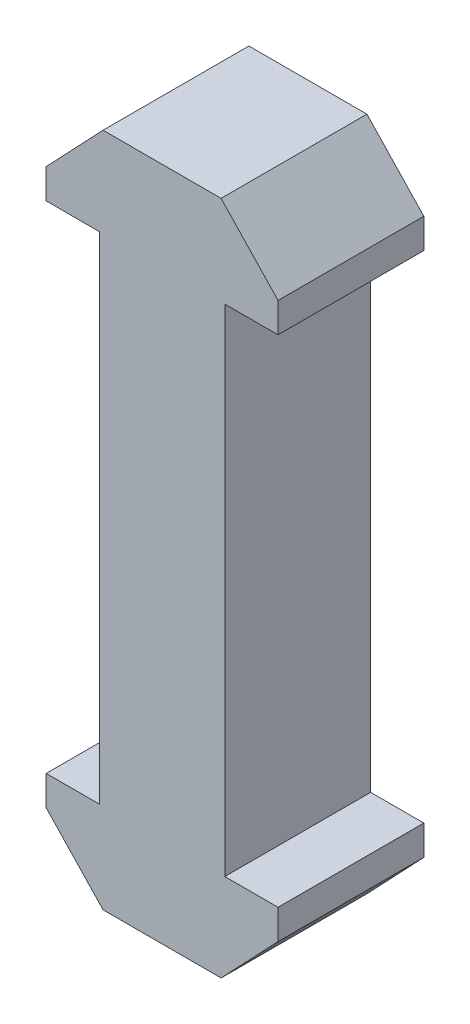
SolidWorks part; units mm, degrees
ref_plane "Front Plane" through (0, 0, 0) normal (0, 0, 1) x (1, 0, 0)
ref_plane "Top Plane" through (0, 0, 0) normal (0, 1, 0) x (1, 0, 0)
ref_plane "Right Plane" through (0, 0, 0) normal (1, 0, 0) x (0, 0, -1)
sketch "Sketch1" plane through (0, 0, 0) normal (0, 0, 1) x (1, 0, 0)
  line L3 (0, 0) -> (0, 14.8775) construction
  line L8 (0, 14.8775) -> (-8.6643, 14.8775) construction
  line L14 (4.3, 31.8775) -> (4.3, -2.1225)
  line L15 (-4.3, 31.8775) -> (-4.3, -2.1225)
  line B0 (7.95, -2.1225) -> (7.95, -4.1625)
  line B1 (4.048, -8.2749) -> (-4.048, -8.2749)
  line B2 (-7.95, -4.1625) -> (-7.95, -2.1225)
  line B3 (-7.95, -2.1225) -> (7.95, -2.1225)
  line B4 (7.95, -4.1625) -> (4.048, -8.2749)
  line B5 (-4.048, -8.2749) -> (-7.95, -4.1625)
  line B6 (7.95, 31.8775) -> (7.95, 33.9175)
  line B7 (4.048, 38.0299) -> (-4.048, 38.0299)
  line B8 (-7.95, 33.9175) -> (-7.95, 31.8775)
  line B9 (-7.95, 31.8775) -> (7.95, 31.8775)
  line B10 (7.95, 33.9175) -> (4.048, 38.0299)
  line B11 (-4.048, 38.0299) -> (-7.95, 33.9175)
  dimension "D1" = 34
  dimension "D5" = 8.6
sketch_block_instance "Block1-1"
sketch_block "Block1" parameters "D1"=8.44, "D2"=2.6, "D3"=6, "D4"=16.7, "D6"=5.6686, "D7"=2.0404, "D8"=8.0963, "D9"=15.9, "D5"=2.4157
sketch_block_instance "Block1-5"
extrude "Boss-Extrude1" add sketch "Sketch1" along normal mid plane 10 contours B0 | L15 B0 L14 | B11 B8 B9 B6 B10 B7 region at (0, 14.8775, 0) region at (0, 34.6191, 0) region at (0, -4.864, 0)
equation "\"SmallJarHeight\"=65"
